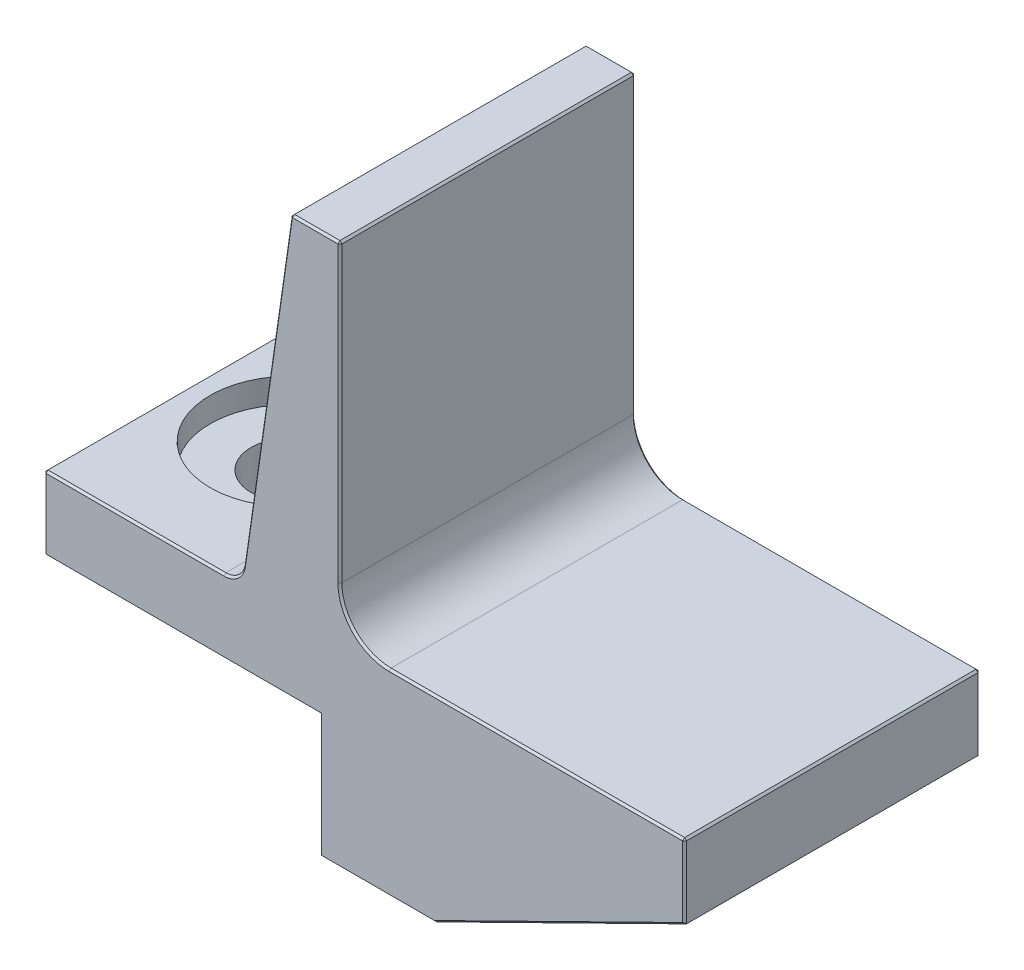
SolidWorks part; units mm, degrees
material "7075-T6 (SN)"
ref_plane "Front Plane" through (0, 0, 0) normal (0, 0, 1) x (1, 0, 0)
ref_plane "Top Plane" through (0, 0, 0) normal (0, 1, 0) x (1, 0, 0)
ref_plane "Right Plane" through (0, 0, 0) normal (1, 0, 0) x (0, 0, -1)
sketch "Sketch1" plane through (0, 0, 0) normal (0, 0, 1) x (1, 0, 0)
  line L0 (0, 0) -> (44.45, 0)
  line L1 (44.45, 0) -> (44.45, -9.525)
  line L2 (-2.6008, -9.525) -> (-38.1608, -9.525)
  line L3 (-38.1608, -9.525) -> (-38.1608, 0)
  line L4 (-38.1608, 0) -> (-12.7608, 0)
  line L5 (-12.7608, 0) -> (-6.35, 44.45)
  line L6 (-6.35, 44.45) -> (0, 44.45)
  line L7 (0, 44.45) -> (0, 0)
  line L8 (-2.6008, -9.525) -> (-2.6008, -25.4)
  line L9 (-2.6008, -25.4) -> (12.2557, -25.4)
  line L10 (12.2557, -25.4) -> (44.45, -9.525)
  point P11 (-8.0723, -9.144)
  dimension "D1" = 44.45
  dimension "D2" = 44.45
  dimension "D3" = 9.525
  dimension "D4" = 38.1608
  dimension "D5" = 6.35
  dimension "D6" = 25.4
  dimension "D7" = 35.56
  dimension "D8" = 9.525
  dimension "D9" = 15.875
extrude "Boss-Extrude1" add sketch "Sketch1" along normal blind 38.1
hole_wizard "CBORE for 3/8 Binding Head Machine Screw1" positions "Sketch6" profile "Sketch3" counterbore size "3/8" standard "ANSI Inch" end condition through all
sketch "Sketch6" plane through (0, 0, 0) normal (0, 1, 0) x (1, 0, 0)
  line L0 (-12.7608, 0) -> (-38.1608, 0) construction
  line L1 (-38.1608, -38.1) -> (-38.1608, 0) construction
  point P0 (-25.4608, -19.05)
  point P5 (-25.4608, 0)
  point P8 (-38.1608, -19.05)
sketch "Sketch3" plane through (-25.4608, 0, 19.05) normal (1, 0, 0) x (0, 0, 1)
  line L0 (0, 0) -> (0, 25.4)
  line L1 (0, 25.4) -> (5.0419, 25.4)
  line L3 (5.0419, 25.4) -> (5.0419, 3.175)
  line L4 (10.3187, 3.175) -> (5.0419, 3.175)
  line L5 (10.3187, 3.175) -> (10.3187, 0)
  line L7 (10.3187, 0) -> (0, 0)
  line L11 (0, 0) -> (0, 107.95) construction
  dimension "Thru Hole Dia." = 10.0838
  dimension "Thru Hole Depth" = 25.4
  dimension "C'Bore Depth" = 3.175
fillet "Fillet1" radius 2.54 1 edges at (-12.7608, 0, 19.05)
fillet "Fillet2" radius 6.35 1 edges at (0, 0, 19.05)
chamfer "Chamfer1" distance 0.254 angle 45 31 edges at (-6.35, 44.45, 19.05) (-3.175, 44.45, 0) (-9.3984, 23.3137, 0) (-13.2978, 0.62, 0) (-26.5608, 0, 0) (-38.1608, -4.7625, 0) (-20.3808, -9.525, 0) (44.45, -4.7625, 0) (25.4, 0, 0) (1.8599, 1.8599, 0) (0, 25.4, 0) (44.45, -4.7625, 38.1) (-20.3808, -9.525, 38.1) (-38.1608, -9.525, 19.05) (-38.1608, -4.7625, 38.1) (-38.1608, 0, 19.05) (-26.5608, 0, 38.1) (-13.2978, 0.62, 38.1) (-9.3984, 23.3137, 38.1) (-3.175, 44.45, 38.1) (0, 44.45, 19.05) (0, 25.4, 38.1) (1.8599, 1.8599, 38.1) (25.4, 0, 38.1) (44.45, 0, 19.05) (-2.6008, -17.4625, 0) (4.8274, -25.4, 0) (28.3528, -17.4625, 0) (28.3528, -17.4625, 38.1) (4.8274, -25.4, 38.1) (-2.6008, -17.4625, 38.1) first distance on face at (-3.175, 44.45, 19.05) first distance on face at (-9.3984, 23.3137, 19.05) first distance on face at (-13.5008, 0.8544, 19.05) first distance on face at (-25.4608, 0, 29.3687) first distance on face at (-38.1608, -4.7625, 19.05) first distance on face at (-30.5027, -9.525, 19.05) first distance on face at (44.45, -4.7625, 19.05) first distance on face at (-0.668, 1.2514, 0) first distance on face at (2.5174, 2.5174, 19.05) first distance on face at (0, 25.4, 19.05) first distance on face at (-0.668, 1.2514, 38.1) first distance on face at (-2.6008, -17.4625, 19.05) first distance on face at (4.8274, -25.4, 19.05) first distance on face at (28.3528, -17.4625, 19.05)
